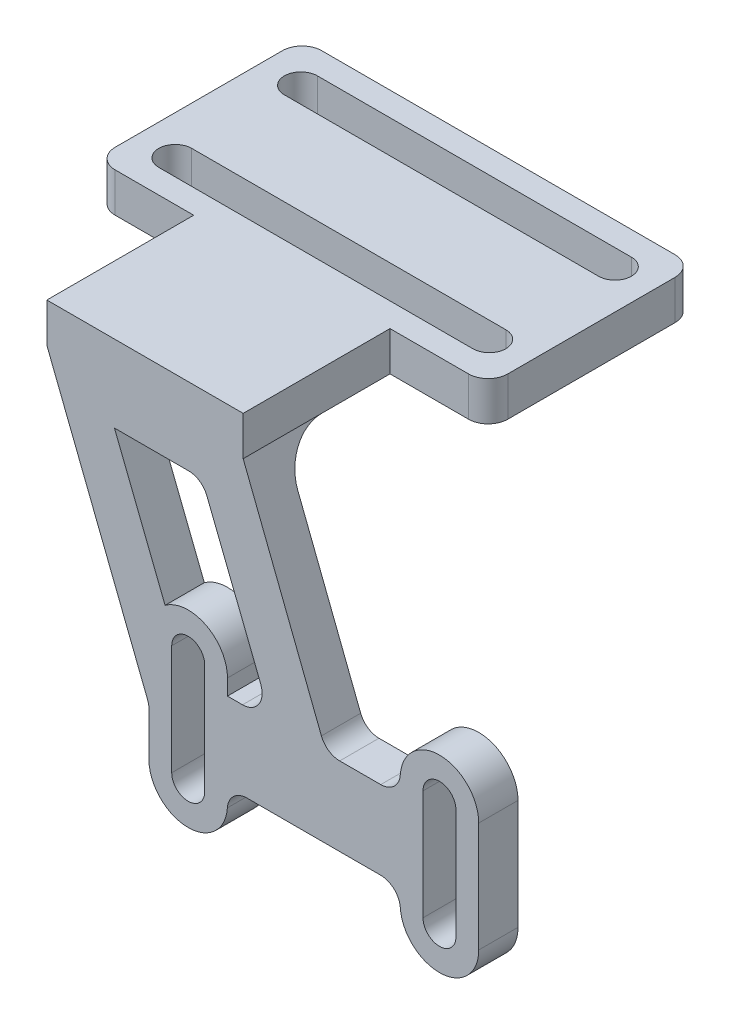
SolidWorks part; units mm, degrees
ref_plane "Front" through (0, 0, 0) normal (0, 0, 1) x (1, 0, 0)
ref_plane "Top" through (0, 0, 0) normal (0, 1, 0) x (1, 0, 0)
ref_plane "Right" through (0, 0, 0) normal (1, 0, 0) x (0, 0, -1)
sketch "Sketch1" plane through (0, 0, 0) normal (0, 1, 0) x (1, 0, 0)
  line L1 (20.5, 3.15) -> (-4.5, 3.15)
  line L2 (-4.5, -5) -> (20.5, -5)
  line L3 (-4.5, -5) -> (-4.5, 3.15)
  line L5 (20.5, -5) -> (20.5, 3.15)
  line L6 (-4.5, -5) -> (15.875, 3.15) construction
  line L7 (0.125, 3.15) -> (20.5, -5) construction
  circle A0 centre (16, 0) radius 2.1
  circle A1 centre (0, 0) radius 2.1
  point P5 (8, 0)
extrude "Boss-Extrude1" add sketch "Sketch1" along normal blind 5 contours L2 A1 A0 region at (8, 0, 1.0706)
sketch "Sketch3" plane through (0, 0, -3.15) normal (0, 0, -1) x (-1, 0, 0)
  line L1 (-20.5, 5) -> (4.5, 5)
  line L2 (-20.5, 5) -> (-20.5, 0)
  line L4 (4.5, 5) -> (4.5, 0)
  line L6 (4.5, 0) -> (-8.5, -33.1011)
  line L8 (-31.0834, -27.1845) -> (-40.5, -27.1845)
  line L9 (-20.5, 0) -> (-31.0834, -27.1845)
  line L10 (-6.0512, -4.8161) -> (-15.2539, -4.8161)
  line L12 (-15.2539, -4.8161) -> (-24.0925, -27.1845)
  line L13 (-24.0925, -27.1845) -> (-18.5, -27.1845)
  line L15 (-4.1055, -4.8161) -> (-6.0512, -4.8161)
  line L16 (-13.5, -25.1845) -> (-13.5, -39.1845) construction
  line L17 (-43.4, -25.1845) -> (-43.4, -39.1845)
  line L18 (-11.4, -25.1845) -> (-11.4, -39.1845)
  line L19 (-15.6, -25.1845) -> (-15.6, -39.1845)
  line L20 (-45.5, -25.1845) -> (-45.5, -39.1845) construction
  line L21 (-47.6, -25.1845) -> (-47.6, -39.1845)
  line L22 (-13.5, -25.1845) -> (-13.5, -39.1845) construction
  line L23 (-8.5, -33.1011) -> (-8.5, -39.1845)
  line L24 (-18.5, -25.1845) -> (-18.5, -27.1845)
  line L25 (-45.5, -25.1845) -> (-45.5, -39.1845) construction
  line L26 (-40.5, -25.1845) -> (-40.5, -27.1845)
  line L27 (-50.5, -25.1845) -> (-50.5, -39.1845)
  line L28 (-18.5, -37.1845) -> (-40.5, -37.1845)
  line L29 (-18.5, -37.1845) -> (-18.5, -39.1845)
  line L30 (-10.5568, -21.1426) -> (-4.1055, -4.8161)
  line L31 (-40.5, -37.1845) -> (-40.5, -39.1845)
  arc A4 (-11.4, -25.1845) -> (-15.6, -25.1845) centre (-13.5, -25.1845) ccw
  arc A5 (-15.6, -39.1845) -> (-11.4, -39.1845) centre (-13.5, -39.1845) ccw
  arc A6 (-43.4, -25.1845) -> (-47.6, -25.1845) centre (-45.5, -25.1845) ccw
  arc A7 (-47.6, -39.1845) -> (-43.4, -39.1845) centre (-45.5, -39.1845) ccw
  arc A8 (-10.5568, -21.1426) -> (-18.5, -25.1845) centre (-13.5, -25.1845) ccw
  arc A9 (-18.5, -39.1845) -> (-8.5, -39.1845) centre (-13.5, -39.1845) ccw
  arc A10 (-40.5, -25.1845) -> (-50.5, -25.1845) centre (-45.5, -25.1845) ccw
  arc A11 (-50.5, -39.1845) -> (-40.5, -39.1845) centre (-45.5, -39.1845) ccw
  point P11 (-29.5, -32.1845)
  point P25 (-45.5, -32.1845)
  point P26 (-13.5, -32.1845)
  point P36 (-13.5, -32.1845)
  point P42 (-45.5, -32.1845)
extrude "Boss-Extrude3" add sketch "Sketch3" along normal blind 5
sketch "Sketch4" plane through (0, 0, -8.15) normal (0, 0, -1) x (-1, 0, 0)
  line L1 (-20.5, 5) -> (4.5, 5)
  line L2 (-20.5, 5) -> (-20.5, 0)
  line L3 (-20.5, 0) -> (4.5, 0)
  line L4 (4.5, 5) -> (4.5, 0)
extrude "Boss-Extrude4" add sketch "Sketch4" along normal blind 40
sketch "Sketch5" plane through (0, 5, 0) normal (0, 1, 0) x (1, 0, 0)
  circle A2 centre (16, 43) radius 2.1
  circle A3 centre (16, 27) radius 2.1
  circle A4 centre (0, 27) radius 2.1
  circle A5 centre (0, 43) radius 2.1
extrude "Cut-Extrude1" cut sketch "Sketch5" against normal blind 8.15
fillet "Fillet1" radius 2.5 11 edges at (-4.5, 2.5, 5) (20.5, 2.5, 5) (31.0834, -27.1845, -5.65) (24.0925, -27.1845, -5.65) (15.2539, -4.8161, -5.65) (-4.5, 2.5, -48.15) (20.5, 2.5, -48.15) (40.5, -27.1845, -5.65) (40.5, -37.1845, -5.65) (18.5, -37.1845, -5.65) (8.5, -33.1011, -5.65)
sketch "Sketch6" plane through (0, 0, 0) normal (0, -1, 0) x (1, 0, 0)
  line L5 (20.5, -3.15) -> (-8.0365, -3.15)
  line L6 (20.5, -3.15) -> (20.5, 7.8533)
  line L7 (20.5, 7.8533) -> (-8.0365, 7.8533)
  line L8 (-8.0365, -3.15) -> (-8.0365, 7.8533)
extrude "Cut-Extrude2" cut sketch "Sketch6" against normal blind 8.15
fillet "Fillet2" radius 5 1 edges at (8, 0, -8.15)
sketch "Sketch7" plane through (0, 5, 0) normal (0, 1, 0) x (1, 0, 0)
  line L0 (0, 43) -> (16, 43)
  line L1 (-12, 43) -> (28, 43) construction
  line L2 (-17, 21.85) -> (33, 21.85)
  line L3 (-17, 21.85) -> (-17, 48.15)
  line L4 (-17, 48.15) -> (33, 48.15)
  line L5 (33, 21.85) -> (33, 48.15)
  line L6 (-17, 21.85) -> (33, 48.15) construction
  line L7 (-17, 48.15) -> (33, 21.85) construction
  line L9 (-12, 45.1) -> (28, 45.1)
  line L10 (-12, 40.9) -> (28, 40.9)
  line L11 (-12, 27) -> (28, 27) construction
  line L12 (-12, 29.1) -> (28, 29.1)
  line L13 (-12, 24.9) -> (28, 24.9)
  arc A0 (-12, 45.1) -> (-12, 40.9) centre (-12, 43) ccw
  arc A1 (28, 40.9) -> (28, 45.1) centre (28, 43) ccw
  arc A2 (-12, 29.1) -> (-12, 24.9) centre (-12, 27) ccw
  arc A3 (28, 24.9) -> (28, 29.1) centre (28, 27) ccw
  point P4 (8, 35)
  point P15 (8, 43)
  point P21 (8, 27)
  line M2 (20.5, 3.15) -> (20.5, 45.65)
  arc M3 (20.5, 45.65) -> (18, 48.15) centre (18, 45.65) ccw
  line M4 (18, 48.15) -> (-2, 48.15)
  arc M5 (-2, 48.15) -> (-4.5, 45.65) centre (-2, 45.65) ccw
  line M6 (-4.5, 45.65) -> (-4.5, 3.15)
extrude "Boss-Extrude6" add sketch "Sketch7" against normal blind 5 contours A3 L13 L2 L5 L4 L9 A1 L10 L12 M2 M3 | L12 L10 M6 M2 | L9 M6 M2 M3 M4 M5 | L13 L2 M6 M2 | A2 L12 L10 A0 L9 L4 L3 L2 L13 M6 M5 region at (-11.2187, 5, -35.0667) region at (8, 5, -23.375) region at (27.2187, 5, -35.0667) region at (8, 5, -46.5898) region at (8, 5, -35)
sketch "Sketch8" plane through (0, 5, 0) normal (0, 1, 0) x (1, 0, 0)
  line L0 (16, 43) -> (0, 43)
  line L1 (-12, 43) -> (28, 43) construction
  line L2 (-12, 45.1) -> (28, 45.1)
  line L3 (-12, 40.9) -> (28, 40.9)
  line L4 (-12, 27) -> (28, 27) construction
  line L6 (-12, 29.1) -> (28, 29.1)
  line L7 (-12, 24.9) -> (28, 24.9)
  arc A0 (-12, 45.1) -> (-12, 40.9) centre (-12, 43) ccw
  arc A1 (28, 40.9) -> (28, 45.1) centre (28, 43) ccw
  arc A2 (-12, 29.1) -> (-12, 24.9) centre (-12, 27) ccw
  arc A3 (28, 24.9) -> (28, 29.1) centre (28, 27) ccw
  point P6 (8, 43)
  point P17 (8, 27)
  line M2 (20.5, 24.9) -> (20.5, 29.1)
  line M6 (20.5, 40.9) -> (20.5, 45.1)
  line M9 (-4.5, 29.1) -> (-4.5, 24.9)
  line M13 (-4.5, 45.1) -> (-4.5, 40.9)
  circle M17 centre (0, 27) radius 2.1
  circle M18 centre (16, 27) radius 2.1
  circle M27 centre (0, 43) radius 2.1
  circle M28 centre (16, 43) radius 2.1
extrude "Cut-Extrude3" cut sketch "Sketch8" against normal blind 5 contours L7 L6 M18 M2 | L7 L6 M17 M18 | L3 L2 M13 M27 | L3 L0 M27 M28 | L7 L6 M9 M17 | L3 L2 M28 M6 | L2 L0 M27 M28 region at (8, 5, -41.9088) region at (8, 5, -44.0912) region at (19.0361, 5, -43) region at (-3.0361, 5, -43) region at (-3.0361, 5, -27) region at (8, 5, -27) region at (19.0361, 5, -27)
fillet "Fillet3" radius 2.5 4 edges at (-17, 2.5, -48.15) (-17, 2.5, -21.85) (33, 2.5, -48.15) (33, 2.5, -21.85)
